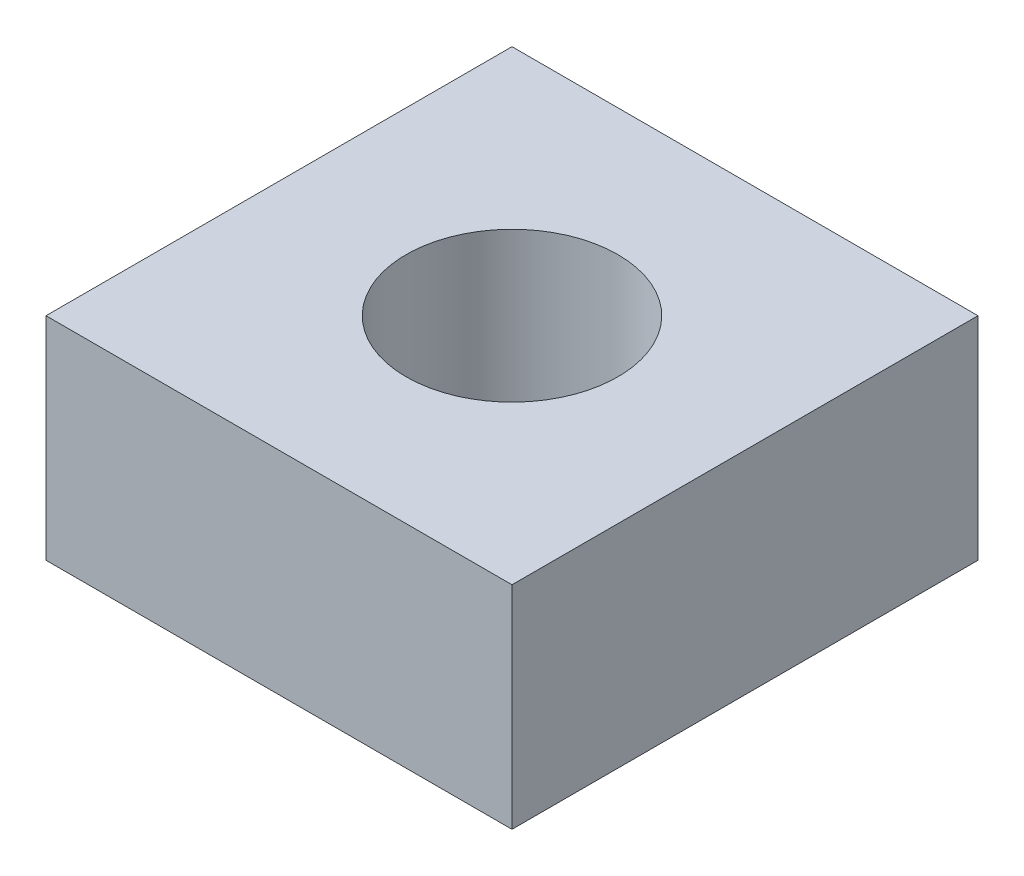
SolidWorks part; units mm, degrees
material "1023 Carbon Steel Sheet (SS)"
ref_plane "Front Plane" through (0, 0, 0) normal (0, 0, 1) x (1, 0, 0)
ref_plane "Top Plane" through (0, 0, 0) normal (0, 1, 0) x (1, 0, 0)
ref_plane "Right Plane" through (0, 0, 0) normal (1, 0, 0) x (0, 0, -1)
sketch "Sketch1" plane through (0, 0, 0) normal (0, 1, 0) x (1, 0, 0)
  line L1 (-2.75, -2.75) -> (2.75, -2.75)
  line L2 (-2.75, -2.75) -> (-2.75, 2.75)
  line L3 (-2.75, 2.75) -> (2.75, 2.75)
  line L4 (2.75, -2.75) -> (2.75, 2.75)
  line L5 (-2.75, -2.75) -> (2.75, 2.75) construction
  line L6 (-2.75, 2.75) -> (2.75, -2.75) construction
  point P0 (0, 0)
  dimension "D1" = 5.5
extrude "Boss-Extrude1" add sketch "Sketch1" along normal mid plane 2.5
sketch "Sketch3" plane through (0, 1.25, 0) normal (0, 1, 0) x (1, 0, 0)
  point P0 (0, 0)
hole_wizard "Tap Drill for M3x0.5 Tap1" positions "3DSketch2" profile "Sketch4" hole size "M3x0.5" standard "ANSI Metric" end condition up to next
sketch3d "3DSketch2"
  point P0 (0, 0, 0)
  point P3 (0, 0, 0)
  point P5 (0, 1.25, 0)
sketch "Sketch4" plane through (0, 1.25, 0) normal (1, 0, 0) x (0, 0, 1)
  line L0 (0, 0) -> (0, 2.501)
  line L1 (0, 2.501) -> (1.25, 2.501)
  line L2 (1.25, 2.501) -> (1.25, 0)
  line L5 (1.25, 0) -> (0, 0)
  line L11 (0, -6.35) -> (0, 107.95) construction
  dimension "Thru Hole Dia." = 2.5
  dimension "Thru Hole Depth" = 2.501
